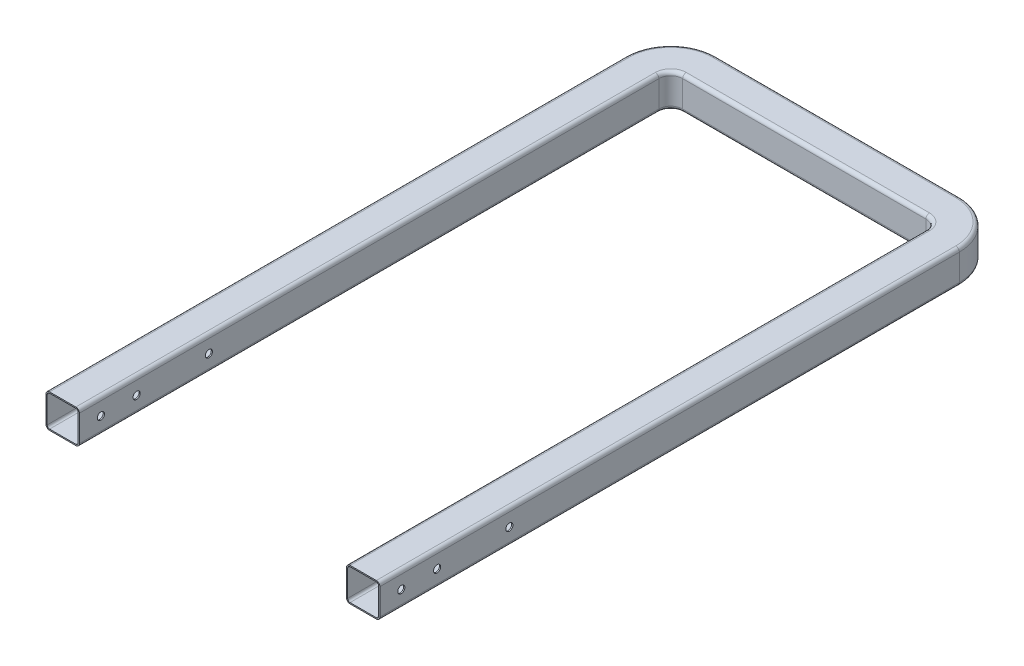
SolidWorks part; units mm, degrees
material "5052-H38, Rod (SS)"
ref_plane "Front Plane" through (0, 0, 0) normal (0, 0, 1) x (1, 0, 0)
ref_plane "Top Plane" through (0, 0, 0) normal (0, 1, 0) x (1, 0, 0)
ref_plane "Right Plane" through (0, 0, 0) normal (1, 0, 0) x (0, 0, -1)
sketch "Sketch1" plane through (0, 0, 0) normal (0, 1, 0) x (1, 0, 0)
  line L0 (0, 0) -> (0, 810)
  line L1 (40, 850) -> (380, 850)
  line L2 (420, 810) -> (420, 0)
  line L3 (0, 560) -> (420, 560) construction
  line L4 (0, 260) -> (420, 260) construction
  line L5 (420, 260) -> (420, 560) construction
  arc A0 (380, 850) -> (420, 810) centre (380, 810) cw
  arc A1 (40, 850) -> (0, 810) centre (40, 810) ccw
  point P7 (420, 850)
  point P10 (0, 850)
  dimension "D3" = 40
  dimension "D4" = 250
  dimension "D1" = 850
  dimension "D2" = 420
  dimension "D5" = 300
ref_plane "Plane1" through (0, 0, 0) normal (0, 0, 1) x (1, 0, 0)
sketch "Sketch3" plane through (0, 0, 0) normal (0, 0, 1) x (1, 0, 0)
  line L1 (-18.35, -23.35) -> (18.35, -23.35)
  line L2 (-23.35, -18.35) -> (-23.35, 18.35)
  line L3 (-18.35, 23.35) -> (18.35, 23.35)
  line L4 (23.35, -18.35) -> (23.35, 18.35)
  line L5 (-23.35, -23.35) -> (23.35, 23.35) construction
  line L6 (-23.35, 23.35) -> (23.35, -23.35) construction
  arc A0 (-18.35, 23.35) -> (-23.35, 18.35) centre (-18.35, 18.35) ccw
  arc A1 (-23.35, -18.35) -> (-18.35, -23.35) centre (-18.35, -18.35) ccw
  arc A2 (18.35, -23.35) -> (23.35, -18.35) centre (18.35, -18.35) ccw
  arc A3 (23.35, 18.35) -> (18.35, 23.35) centre (18.35, 18.35) ccw
  point P0 (0, 0)
  dimension "D3" = 5
  dimension "D1" = 46.7
  dimension "D2" = 46.7
sweep "Sweep-Thin1" add profiles "Sketch3" path "Sketch1" parameters "D1"=1.65
sketch "Sketch4" plane through (0, 0, 0) normal (1, 0, 0) x (0, 0, -1)
  line L0 (0, 0) -> (810, 0) construction
  circle A0 centre (30, 0) radius 5
  circle A1 centre (80, 0) radius 5
  circle A2 centre (180.9551, 0) radius 5
  dimension "D1" = 30
  dimension "D3" = 10
  dimension "D2" = 80
extrude "Cut-Extrude2" cut sketch "Sketch4" against normal through all both and the other way through all
ref_plane "Plane4" through (420, 0, 0) normal (-1, 0, 0) x (0, 0, 1)
sketch "Sketch8" plane through (420, 0, 0) normal (-1, 0, 0) x (0, 0, 1)
  line L0 (-560, 0) -> (-260, 0) construction
  line L1 (-410, 0) -> (-410, -61.9086) construction
ref_plane "Plane5" through (0, 0, 0) normal (1, 0, 0) x (0, 0, -1)
